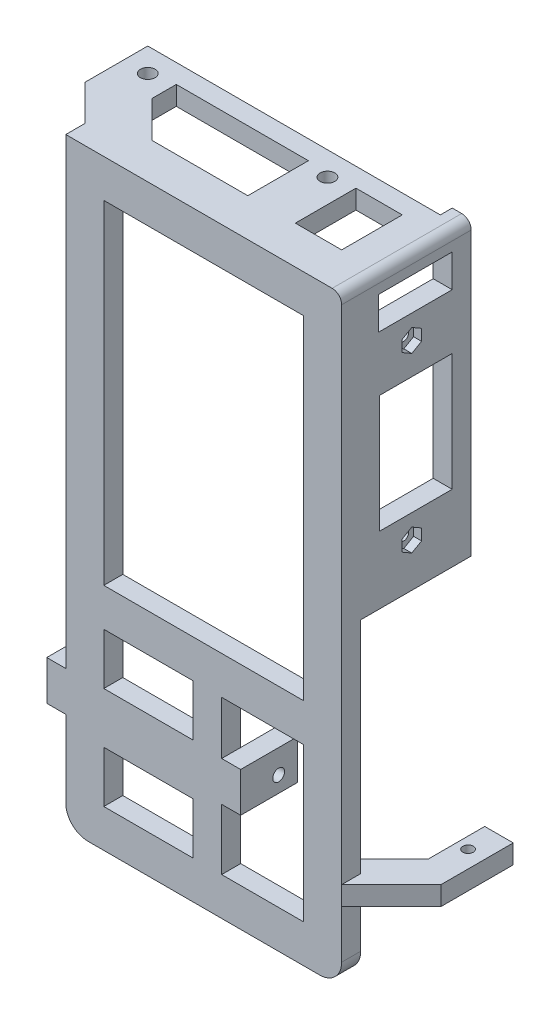
SolidWorks part; units mm, degrees
ref_plane "前视基准面" through (0, 0, 0) normal (0, 0, 1) x (1, 0, 0)
ref_plane "上视基准面" through (0, 0, 0) normal (0, 1, 0) x (1, 0, 0)
ref_plane "右视基准面" through (0, 0, 0) normal (1, 0, 0) x (0, 0, -1)
other "Configuration Table"
sketch "草图4" plane through (37.65, 0, 0) normal (1, 0, 0) x (0, 0, -1)
  line L1 (7.255, 53.1366) -> (23.255, 53.1366) construction
  line L2 (19.8734, 110.55) -> (11.6366, 110.55)
  line L3 (23.255, 110.55) -> (0, 110.55)
  line L4 (0, 53.1366) -> (23.255, 53.1366)
  line L5 (0, 110.55) -> (0, 53.1366)
  line L6 (23.255, 110.55) -> (23.255, 53.1366)
  line L7 (19.8734, 109.55) -> (11.6366, 109.55) construction
  line L8 (0, -7.25) -> (0, 31.75) construction
  line L9 (19.8734, 109.55) -> (11.6366, 109.55)
  line L11 (23.255, 107.6634) -> (23.255, 53.1366) construction
  circle M6 centre (10.755, 57.65) radius 1.1
  circle M7 centre (10.755, 62.3) radius 1
  circle M8 centre (10.755, 94.05) radius 1.1
  arc M9 (11.755, 97.8871) -> (9.755, 97.8871) centre (10.755, 98.67) cw
  line M10 (9.755, 97.8871) -> (9.755, 99.4529)
  arc M11 (9.755, 99.4529) -> (11.755, 99.4529) centre (10.755, 98.67) cw
  line M12 (11.755, 99.4529) -> (11.755, 97.8871)
  line M13 (7.255, 53.1366) -> (23.255, 53.1366)
  line M15 (23.255, 107.6634) -> (7.255, 107.6634)
  line M16 (7.255, 107.6634) -> (7.255, 53.1366)
  dimension "D1" = 1
extrude "凸台-拉伸5" add sketch "草图4" along normal blind 4 separate body contours M8 | M9 M12 M11 M10 | L6 L3 L5 L4 M16 M15 | M6 | L6 M15 M16 M13 M7 M12 M9 M10 M11 M8 M6 | M7 region at (37.65, 84.5646, -4.7881) region at (37.65, 80.411, -15.335) region at (37.65, 57.65, -10.755) region at (37.65, 62.3, -10.755) region at (37.65, 94.05, -10.755) region at (37.65, 98.67, -10.755)
sketch "草图5" plane through (0, 110.55, 0) normal (0, 1, 0) x (1, 0, 0)
  line L0 (41.65, 23.255) -> (41.65, 0) construction
  line L1 (41.65, 0) -> (37.65, 0) construction
  line L2 (41.65, 20.755) -> (-23.9, 20.755)
  line L3 (41.65, 20.755) -> (41.65, 0)
  line L4 (41.65, 0) -> (-23.9, 0)
  line L5 (-23.9, 20.755) -> (-23.9, 0)
  circle A0 centre (-18.9, 15.755) radius 1.55
  circle A1 centre (18.9, 15.755) radius 1.55
  point P6 (0, 0)
  point P13 (0, 0)
  dimension "D2" = 3.1
  dimension "D1" = 5
  dimension "D3" = 5
extrude "凸台-拉伸6" add sketch "草图5" along normal blind 4
sketch "草图7" plane through (0, 0, 0) normal (0, 0, 1) x (1, 0, 0)
  line L5 (41.65, 114.55) -> (41.65, 53.1366) construction
  line L6 (-11.75, -11.9) -> (11.75, -11.9) construction
  line L7 (-23.9, 114.55) -> (41.65, 114.55)
  line L8 (-23.9, 114.55) -> (-23.9, -11.9)
  line L9 (-23.9, -11.9) -> (41.65, -11.9)
  line L10 (41.65, 114.55) -> (41.65, -11.9)
extrude "凸台-拉伸8" add sketch "草图7" along normal blind 4
sketch "草图11" plane through (0, 0, 0) normal (0, 0, -1) x (-1, 0, 0)
  line L0 (-33.65, -3.9) -> (-33.65, 110.55)
  line L1 (-33.65, -3.9) -> (8.4, -3.9)
  line L3 (8.4, -3.9) -> (8.4, 110.55)
  line L4 (-37.65, 110.55) -> (23.9, 110.55) construction
  line L5 (23.9, -11.9) -> (-41.65, -11.9) construction
  line L6 (16.4, -7.25) -> (16.4, 21.75) construction
  line L7 (-10.4, -3.9) -> (-10.4, 28.4)
  line L8 (-10.4, 28.4) -> (8.4, 28.4)
  line L9 (8.4, 28.4) -> (8.4, 36.4)
  line L10 (8.4, 36.4) -> (-16.4, 36.4)
  line L11 (-16.4, 36.4) -> (-16.4, -3.9)
  line L12 (-16.4, 60.55) -> (-16.4, 21.75) construction
  line L13 (11.32, 36.4) -> (-11.32, 36.4) construction
  line L14 (8.4, 6.9) -> (-10.4, 6.9)
  line L15 (-10.4, 17.6) -> (8.4, 17.6)
  line L16 (9.52, 15.6) -> (-9.52, 15.6) construction
  line L17 (-11.32, 8.9) -> (11.32, 8.9) construction
  line L18 (-16.4, 60.55) -> (-16.4, -7.25) construction
  line L19 (-10.73, -11.9) -> (-6.52, -11.9) construction
  line L20 (-16.4, 60.55) -> (-16.4, -7.25)
  line L21 (-11.75, -11.9) -> (11.75, -11.9)
  line L22 (16.4, -7.25) -> (16.4, 31.75)
  line L23 (8.4, 36.4) -> (11.75, 36.4)
  line L24 (16.4, 31.75) -> (16.4, 110.55)
  line L25 (23.9, 110.55) -> (-37.65, 110.55) construction
  line L26 (8.4, 110.55) -> (23.9, 110.55)
  line L27 (23.9, 110.55) -> (23.9, -11.9) construction
  line L28 (23.9, 110.55) -> (23.9, -11.9)
  line L29 (23.9, -11.9) -> (-41.65, -11.9)
  line L30 (-33.65, 110.55) -> (23.9, 110.55)
  line L31 (-41.65, -11.9) -> (-41.65, 53.1366) construction
  line L32 (23.9, 106.55) -> (-33.65, 106.55)
  line L33 (-41.65, 114.55) -> (23.9, 114.55) construction
  line L34 (-10.4, 28.4) -> (-33.65, 28.4)
  line L35 (-16.4, 36.4) -> (-33.65, 36.4)
  arc A0 (16.4, 31.75) -> (11.75, 36.4) centre (11.75, 31.75) ccw construction
  arc A1 (-16.4, -7.25) -> (-11.75, -11.9) centre (-11.75, -7.25) ccw construction
  arc A2 (11.75, -11.9) -> (16.4, -7.25) centre (11.75, -7.25) ccw construction
  arc A3 (16.4, 31.75) -> (11.75, 36.4) centre (11.75, 31.75) ccw
  arc A4 (-16.4, -7.25) -> (-11.75, -11.9) centre (-11.75, -7.25) ccw
  arc A5 (11.75, -11.9) -> (16.4, -7.25) centre (11.75, -7.25) ccw
  point P51 (-16.4, 28.4)
  line M8 (-41.65, -11.9) -> (23.9, -11.9)
  line M9 (23.9, -11.9) -> (23.9, 110.55)
  dimension "D1" = 8
  dimension "D2" = 8
  dimension "D3" = 8
  dimension "D4" = 6
  dimension "D5" = 2
  dimension "D6" = 2
  dimension "D7" = 8
  dimension "D8" = 8
extrude "切除-拉伸3" cut sketch "草图11" against normal through all contours L3 L32 L0 L1 L11 L10 | L7 L15 L3 L8 | L3 L14 L7 L1 | A5 L32 L24 L22 M8 M9 | L11 L34 L0 L1 region at (25.025, 12.25, 0) region at (12.625, 71.475, 0) region at (1, 1.5, 0) region at (1, 23, 0) region at (-20.1251, 47.0227, 0)
sketch "草图12" plane through (0, 2.8903, 0) normal (0, 1, 0) x (1, 0, 0)
  line L0 (52.0958, 21.655) -> (52.0958, 9.855)
  line L1 (46.0958, 9.855) -> (36.2408, 0)
  line L2 (-11.75, 0) -> (41.65, 0) construction
  line L3 (52.0958, 9.855) -> (52.0958, 6.4458)
  line L5 (52.0958, 6.4458) -> (41.65, -4)
  line L6 (36.2408, 0) -> (41.65, -4)
  line L7 (50.7958, 9.855) -> (50.7958, 15.105)
  line L8 (50.7958, 15.105) -> (49.2557, 15.105)
  line L9 (49.2557, 16.405) -> (50.7958, 16.405)
  line L10 (50.7958, 16.405) -> (50.7958, 21.655)
  line L11 (50.7958, 21.655) -> (46.0958, 21.655)
  line L12 (46.0958, 21.655) -> (46.0958, 9.855)
  line L13 (46.0958, 9.855) -> (50.7958, 9.855)
  line L18 (52.0958, 21.655) -> (46.0958, 21.655)
  line L19 (46.0958, 21.655) -> (46.0958, 9.855)
  line L20 (46.0958, 9.855) -> (52.0958, 9.855)
  arc A1 (49.2557, 16.405) -> (49.2557, 15.105) centre (48.4958, 15.755) ccw
  line M13 (50.7958, 9.855) -> (50.7958, 15.105)
  line M14 (50.7958, 15.105) -> (49.2557, 15.105)
  arc M15 (49.2557, 15.105) -> (49.2557, 16.405) centre (48.4958, 15.755) cw
  line M16 (49.2557, 16.405) -> (50.7958, 16.405)
  line M17 (50.7958, 16.405) -> (50.7958, 21.655)
  line M18 (50.7958, 21.655) -> (46.0958, 21.655)
  line M19 (46.0958, 21.655) -> (46.0958, 9.855)
  line M20 (46.0958, 9.855) -> (50.7958, 9.855)
  dimension "D2" = 6
  dimension "D3" = 45
  dimension "D1" = 0
extrude "凸台-拉伸9" add sketch "草图12" along normal blind 4 contours M20 M13 M14 M15 M16 M17 M18 M19 | L20 L1 L6 L5 L3 M20 | L20 L0 L18 M13 M17 M16 M15 M14 region at (50.8703, 2.8903, -15.755) region at (44.6332, 2.8903, -3.6048) region at (50.6687, 2.8903, -19.03)
sketch "草图13" plane through (0, 110.55, 0) normal (0, -1, 0) x (1, 0, 0)
  line L0 (-23.9, -7.5) -> (-16.4, 0)
  line L1 (-23.9, -20.755) -> (-23.9, 0) construction
  line L4 (-16.4, 4) -> (-16.4, 0) construction
  line L5 (-16.4, 4) -> (-16.4, 0)
  line L6 (-16.4, 4) -> (-23.9, 4)
  line L7 (-23.9, 4) -> (-23.9, -7.5)
  dimension "D1" = 45
extrude "切除-拉伸4" cut sketch "草图13" against normal mid plane 20
sketch "草图14" plane through (0, 110.55, 0) normal (0, -1, 0) x (1, 0, 0)
  line L0 (37.65, -20.755) -> (-23.9, -20.755) construction
  line L1 (33.65, -16.755) -> (23.9, -16.755)
  line L2 (33.65, -16.755) -> (33.65, -4)
  line L3 (33.65, -4) -> (23.9, -4)
  line L4 (23.9, -16.755) -> (23.9, -4)
  line L5 (13.9, -16.755) -> (-13.9, -16.755)
  line L6 (13.9, -16.755) -> (13.9, -4)
  line L7 (13.9, -4) -> (-6.2579, -4)
  line L8 (-13.9, -16.755) -> (-13.9, -11.6421)
  line L9 (37.65, 0) -> (37.65, -23.255) construction
  line L10 (-8.4, 0) -> (33.65, 0) construction
  line L11 (-13.9, -11.6421) -> (-6.2579, -4)
  line L12 (-23.9, -7.5) -> (-16.4, 0) construction
  circle A0 centre (18.9, -15.755) radius 1.55 construction
  circle A1 centre (-18.9, -15.755) radius 1.55 construction
  dimension "D4" = 5
  dimension "D1" = 4
  dimension "D2" = 4
  dimension "D3" = 4
  dimension "D5" = 5
  dimension "D6" = 5
  dimension "D7" = 10
extrude "切除-拉伸5" cut sketch "草图14" against normal blind 10
sketch "草图16" plane through (37.65, 0, 0) normal (-1, 0, 0) x (0, 0, 1)
  line L0 (-23.255, 53.1366) -> (-23.255, 110.55) construction
  line L1 (-19.255, 67.3) -> (-4, 67.3)
  line L2 (-19.255, 67.3) -> (-19.255, 92.05)
  line L3 (-19.255, 92.05) -> (-4, 92.05)
  line L4 (-4, 67.3) -> (-4, 92.05)
  line L5 (0, -7.25) -> (0, 110.55) construction
  line L6 (-7.5, 110.55) -> (0, 110.55) construction
  line L7 (-19.255, 103.67) -> (-3.75, 103.67)
  line L8 (-19.255, 103.67) -> (-19.255, 110.55)
  line L9 (-19.255, 110.55) -> (-3.75, 110.55)
  line L10 (-3.75, 103.67) -> (-3.75, 110.55)
  circle A0 centre (-10.755, 62.3) radius 1 construction
  circle A1 centre (-10.755, 94.05) radius 1.1 construction
  arc A2 (-9.755, 99.4529) -> (-11.755, 99.4529) centre (-10.755, 98.67) ccw construction
  dimension "D1" = 4
  dimension "D2" = 4
  dimension "D3" = 5
  dimension "D4" = 2
  dimension "D5" = 5
extrude "切除-拉伸6" cut sketch "草图16" against normal through all
sketch "草图2" plane through (-16.4, 0, 0) normal (-1, 0, 0) x (0, 0, 1)
  line L1 (-11.22, 8.9) -> (-4.3571, 8.9) construction
  line L3 (-11.22, 8.9) -> (4, 8.9)
  line L16 (4, -7.25) -> (4, 114.55) construction
  line L17 (-11.22, 15.6) -> (0, 15.6) construction
  line L18 (-11.22, 15.6) -> (4, 15.6)
  line L19 (-8.4892, 12.25) -> (2.3386, 12.25) construction
  line L20 (4, 15.6) -> (4, 8.9)
  line L21 (4, 15.6) -> (4, 17.25)
  line L22 (4, 17.25) -> (-8, 17.25)
  line L23 (-8, 17.25) -> (-8, 8.9)
  line L24 (0, -7.25) -> (0, 110.55) construction
  circle A1 centre (-4, 12.25) radius 1.25
  arc M32 (-4.5, 8.55) -> (-4, 9.05) centre (-4, 8.55) cw
  line M33 (-4, 9.05) -> (0, 9.05)
  line M34 (0, 9.05) -> (0, 27.55)
  dimension "D2" = 5
  dimension "D4" = 4
  dimension "D1" = 2.5
  dimension "D3" = 4
extrude "凸台-拉伸2" add sketch "草图2" along normal blind 4 contours L20 L18 L3 M34 M33 M32 | L19 L23 L3 A1 M32 M33 M34 | L23 L19 A1 L18 M34 | L22 L23 L18 M34 | L21 L22 L18 M34 region at (-16.4, 10.4995, -4.0504) region at (-16.4, 12.174, 1.9043) region at (-16.4, 14.0404, -4) region at (-16.4, 16.425, -4) region at (-16.4, 16.425, 2)
mirror "镜向10" about plane through (0, 0, 0) normal (1, 0, 0) of "凸台-拉伸2"
sketch "草图19" plane through (0, 2.8903, 0) normal (0, -1, 0) x (1, 0, 0)
  circle A0 centre (48.4958, -15.755) radius 1.1
  arc A1 (49.2557, -15.105) -> (49.2557, -16.405) centre (48.4958, -15.755) ccw construction
  dimension "D1" = 2.2
extrude "切除-拉伸7" cut sketch "草图19" against normal up to next
sketch "草图21" plane through (0, 110.55, 0) normal (0, 1, 0) x (1, 0, 0)
  line L4 (37.65, 20.755) -> (41.65, 20.755)
  line L5 (41.65, 20.755) -> (41.65, 23.255)
  line L6 (41.65, 23.255) -> (37.65, 23.255)
  line L7 (41.65, 20.755) -> (41.65, 23.255)
  line L8 (37.65, 20.755) -> (41.65, 20.755)
  line L10 (41.65, 23.255) -> (37.65, 23.255)
  line L12 (37.65, 23.255) -> (37.65, 20.755)
  line L13 (37.65, 23.255) -> (37.65, 20.755)
  dimension "D1" = 0
extrude "凸台-拉伸11" add sketch "草图21" along normal up to surface (4 mm away) up to face at (28.775, 114.55, -10.3775)
fillet "圆角2" radius 2 3 edges at (41.65, 114.55, -9.6275) (37.65, 110.55, -20.005) (37.65, 110.55, -1.875)
fillet "圆角3" radius 4.65 1 edges at (41.65, -11.9, 2)
sketch "草图24" plane through (37.65, 0, 0) normal (-1, 0, 0) x (0, 0, 1)
  line L0 (-9.755, 97.8871) -> (-9.755, 99.4529) construction
  line L1 (-11.755, 97.8871) -> (-11.755, 99.4529) construction
  line L2 (-9.755, 97.8871) -> (-9.755, 99.4529)
  line L3 (-11.755, 97.8871) -> (-11.755, 99.4529)
  arc A0 (-9.755, 99.4529) -> (-11.755, 99.4529) centre (-10.755, 98.67) ccw construction
  arc A1 (-11.755, 97.8871) -> (-9.755, 97.8871) centre (-10.755, 98.67) ccw construction
  circle A2 centre (-10.755, 62.3) radius 1 construction
  arc A3 (-9.755, 99.4529) -> (-11.755, 99.4529) centre (-10.755, 98.67) ccw
  arc A4 (-11.755, 97.8871) -> (-9.755, 97.8871) centre (-10.755, 98.67) ccw
  circle A5 centre (-10.755, 62.3) radius 1
  circle A6 centre (-10.755, 98.67) radius 1
  line M5 (-4, 67.3) -> (-19.255, 67.3)
extrude "切除-拉伸10" cut sketch "草图24" against normal through all contours A5 | A6 M5 region at (37.65, 98.67, -10.755) region at (37.65, 62.3, -10.755)
sketch "草图25" plane through (37.65, 0, 0) normal (-1, 0, 0) x (0, 0, 1)
  circle A12 centre (-10.755, 57.65) radius 1
  circle A13 centre (-10.755, 57.65) radius 1
  circle A15 centre (-10.755, 94.05) radius 1
  circle A16 centre (-10.755, 94.05) radius 1
  dimension "D1" = 0.1
  dimension "D2" = 0.1
extrude "凸台-拉伸12" add sketch "草图25" along normal blind 1
fillet "圆角4" radius 1 2 edges at (36.65, 93.05, -10.755) (36.65, 56.65, -10.755)
sketch "草图27" plane through (41.65, 0, 0) normal (1, 0, 0) x (0, 0, -1)
  line L1 (10.755, 96.3029) -> (12.805, 97.4864)
  line L2 (12.805, 97.4864) -> (12.805, 99.8536)
  line L3 (12.805, 99.8536) -> (10.755, 101.0371)
  line L4 (10.755, 101.0371) -> (8.705, 99.8536)
  line L5 (8.705, 99.8536) -> (8.705, 97.4864)
  line L6 (8.705, 97.4864) -> (10.755, 96.3029)
  line L7 (10.755, 59.9329) -> (12.805, 61.1164)
  line L8 (12.805, 61.1164) -> (12.805, 63.4836)
  line L9 (12.805, 63.4836) -> (10.755, 64.6671)
  line L10 (10.755, 64.6671) -> (8.705, 63.4836)
  line L11 (8.705, 63.4836) -> (8.705, 61.1164)
  line L12 (8.705, 61.1164) -> (10.755, 59.9329)
  circle A0 centre (10.755, 98.67) radius 2.05 construction
  circle A1 centre (10.755, 62.3) radius 2.05 construction
  dimension "D1" = 4.1
extrude "切除-拉伸11" cut sketch "草图27" against normal blind 1.68
